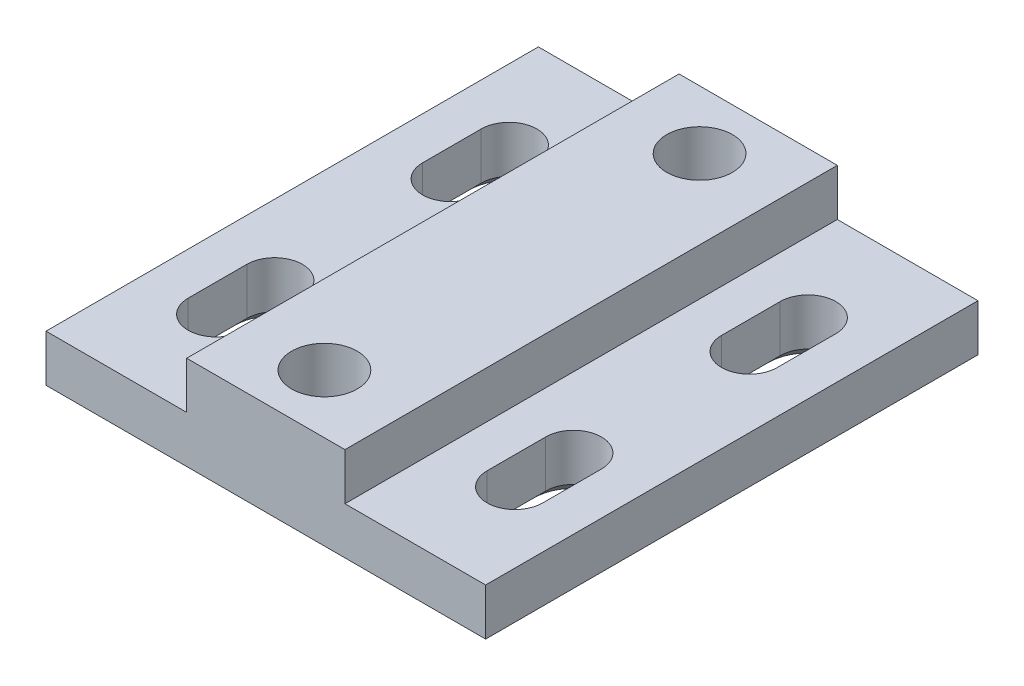
SolidWorks part; units mm, degrees
note: The reader was unsure of these and kept them because the rebuilt part matched: shared geometry of "Esboço1<3>".
ref_plane "Plano frontal" through (0, 0, 0) normal (0, 0, 1) x (1, 0, 0)
ref_plane "Plano superior" through (0, 0, 0) normal (0, 1, 0) x (1, 0, 0)
ref_plane "Plano direito" through (0, 0, 0) normal (1, 0, 0) x (0, 0, -1)
sketch "Esboço1" plane through (0, 0, 0) normal (0, 1, 0) x (1, 0, 0)
  line L0 (-12.75, 7.5) -> (-12.75, 12.5) construction
  line L1 (-18.75, 21) -> (18.75, 21)
  line L2 (-18.75, 21) -> (-18.75, -21)
  line L3 (-18.75, -21) -> (18.75, -21)
  line L4 (18.75, 21) -> (18.75, -21)
  line L5 (-18.75, 21) -> (18.75, -21) construction
  line L6 (-18.75, -21) -> (18.75, 21) construction
  line L7 (-6.75, -21) -> (6.75, -21)
  line L8 (-6.75, -21) -> (-6.75, 21)
  line L9 (-6.75, 21) -> (6.75, 21)
  line L10 (6.75, -21) -> (6.75, 21)
  line L11 (-6.75, -21) -> (6.75, 21) construction
  line L12 (-6.75, 21) -> (6.75, -21) construction
  line L13 (-15.125, 7.5) -> (-15.125, 12.5)
  line L14 (-10.375, 7.5) -> (-10.375, 12.5)
  line L15 (-12.75, -12.5) -> (-12.75, -7.5) construction
  line L16 (-15.125, -12.5) -> (-15.125, -7.5)
  line L17 (-10.375, -12.5) -> (-10.375, -7.5)
  line L18 (0, 32.4237) -> (0, -41.6464) construction
  line L19 (12.75, -12.5) -> (12.75, -7.5) construction
  line L20 (15.125, -12.5) -> (15.125, -7.5)
  line L21 (10.375, -12.5) -> (10.375, -7.5)
  line L22 (12.75, 7.5) -> (12.75, 12.5) construction
  line L23 (15.125, 7.5) -> (15.125, 12.5)
  line L24 (10.375, 7.5) -> (10.375, 12.5)
  circle A0 centre (0, 16) radius 2.8
  circle A1 centre (0, -16) radius 2.8
  arc A2 (15.125, -12.5) -> (10.375, -12.5) centre (12.75, -12.5) cw
  arc A3 (10.375, -7.5) -> (15.125, -7.5) centre (12.75, -7.5) cw
  arc A4 (-15.125, 7.5) -> (-10.375, 7.5) centre (-12.75, 7.5) ccw
  arc A5 (-15.125, -12.5) -> (-10.375, -12.5) centre (-12.75, -12.5) ccw
  arc A6 (-10.375, 12.5) -> (-15.125, 12.5) centre (-12.75, 12.5) ccw
  arc A7 (-10.375, -7.5) -> (-15.125, -7.5) centre (-12.75, -7.5) ccw
  arc A8 (15.125, 7.5) -> (10.375, 7.5) centre (12.75, 7.5) cw
  arc A9 (10.375, 12.5) -> (15.125, 12.5) centre (12.75, 12.5) cw
  point P0 (0, 0)
  point P18 (0, 0)
  point P23 (-12.75, 10)
  point P28 (-12.75, -10)
  point P33 (12.75, -10)
  point P40 (12.75, 10)
  point P45 (-12.75, 7.5)
  point P46 (-10.375, 7.5)
  dimension "D1" = 5.6
  dimension "D2" = 5.6
  dimension "D16" = 42
  dimension "D17" = 32
  dimension "D18" = 16
  dimension "D19" = 13.5
  dimension "D3" = 4.75
  dimension "D7" = 6
  dimension "D6" = 4.75
  dimension "D11" = 11
  dimension "D15" = 5
  dimension "D20" = 5
  dimension "D4" = 20
  dimension "D5" = 6
extrude "Ressalto-extrusão1" add sketch "Esboço1" along normal blind 5
sketch "Esboço2" plane through (0, 5, 0) normal (0, 1, 0) x (1, 0, 0)
  line L1 (5.0229, 16) -> (2.5115, 20.35)
  line L2 (2.5115, 20.35) -> (-2.5115, 20.35)
  line L3 (-2.5115, 20.35) -> (-5.0229, 16)
  line L4 (-5.0229, 16) -> (-2.5115, 11.65)
  line L5 (-2.5115, 11.65) -> (2.5115, 11.65)
  line L6 (2.5115, 11.65) -> (5.0229, 16)
  line L7 (5.0229, -16) -> (2.5115, -11.65)
  line L8 (2.5115, -11.65) -> (-2.5115, -11.65)
  line L9 (-2.5115, -11.65) -> (-5.0229, -16)
  line L10 (-5.0229, -16) -> (-2.5115, -20.35)
  line L11 (-2.5115, -20.35) -> (2.5115, -20.35)
  line L12 (2.5115, -20.35) -> (5.0229, -16)
  circle A0 centre (0, 16) radius 4.35 construction
  circle A1 centre (0, -16) radius 4.35 construction
  dimension "D1" = 8.7
  dimension "D2" = 8.7
extrude "Corte-extrusão1" cut sketch "Esboço2" along normal blind 4 from vertex
extrude "Ressalto-extrusão2" add sketch "Esboço1<3>" along normal blind 4 from vertex at 5 contours L3 L10 L1 L8 A1 A0 starting at point (-18.75, 5, 21)
sketch "Esboço1<3>" plane through (0, 0, 0) normal (0, 1, 0) x (1, 0, 0) same geometry as "Esboço1"
chamfer "Chanfro1" distance 1 angle 45 32 edges at (0, 0, 20.35) (-3.7672, 0, 18.175) (-3.7672, 0, 13.825) (0, 0, 11.65) (3.7672, 0, 13.825) (3.7672, 0, 18.175) (18.75, 0, 0) (0, 0, -21) (-18.75, 0, 0) (0, 0, 21) (0, 0, -11.65) (-3.7672, 0, -13.825) (-3.7672, 0, -18.175) (0, 0, -20.35) (3.7672, 0, -18.175) (3.7672, 0, -13.825) (12.75, 0, -14.875) (15.125, 0, -10) (12.75, 0, -5.125) (10.375, 0, -10) (12.75, 0, 5.125) (15.125, 0, 10) (12.75, 0, 14.875) (10.375, 0, 10) (-10.375, 0, -10) (-12.75, 0, -5.125) (-15.125, 0, -10) (-12.75, 0, -14.875) (-10.375, 0, 10) (-12.75, 0, 14.875) (-15.125, 0, 10) (-12.75, 0, 5.125)
equation "\"D2@Esboço1\"=\"D1@Esboço1\""
equation "\"D18@Esboço1\"=\"D17@Esboço1\"/2"
equation "\"D2@Esboço2\"=\"D1@Esboço2\""
equation "\"D6@Esboço1\"=\"D3@Esboço1\""
equation "\"D15@Esboço1\"=\"D20@Esboço1\""
equation "\"D7@Esboço1\"=\"D5@Esboço1\""
